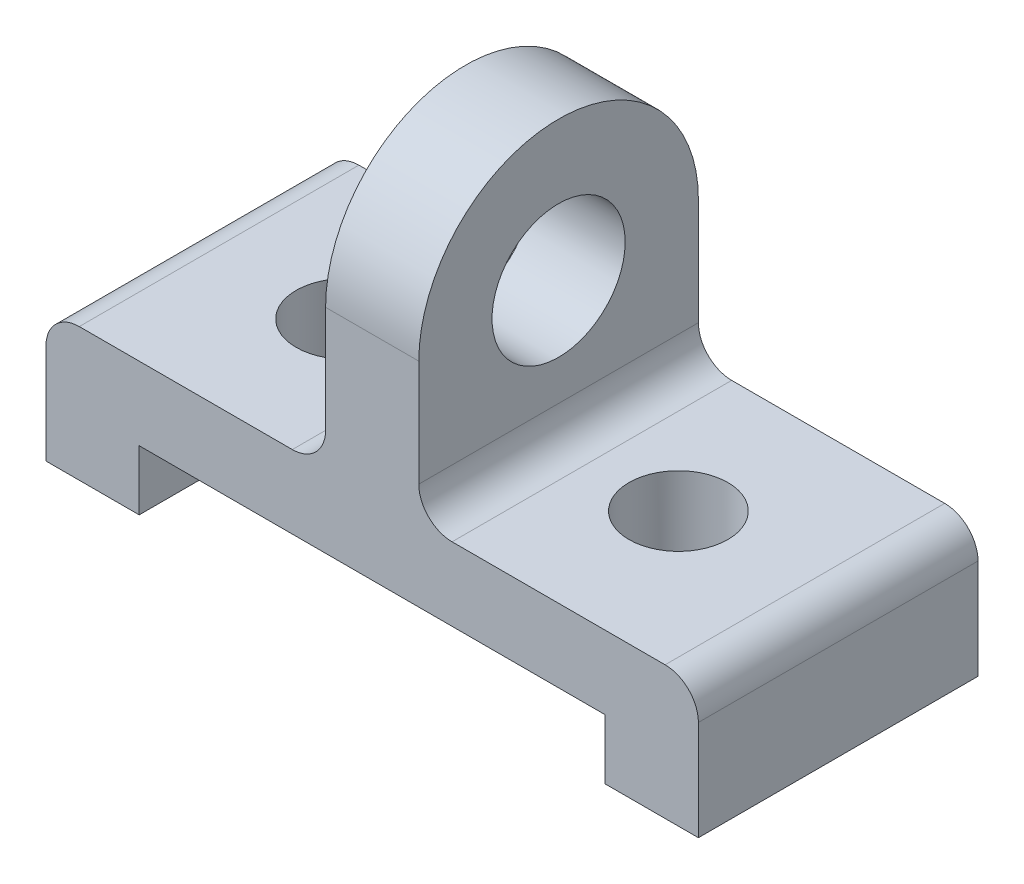
SolidWorks part; units mm, degrees
ref_plane "Front Plane" through (0, 0, 0) normal (0, 0, 1) x (1, 0, 0)
ref_plane "Top Plane" through (0, 0, 0) normal (0, 1, 0) x (1, 0, 0)
ref_plane "Right Plane" through (0, 0, 0) normal (1, 0, 0) x (0, 0, -1)
sketch "Sketch1" plane through (0, 0, 0) normal (0, 1, 0) x (1, 0, 0)
  line L1 (-49, -21) -> (49, -21)
  line L2 (-49, -21) -> (-49, 21)
  line L3 (-49, 21) -> (49, 21)
  line L4 (49, -21) -> (49, 21)
  line L5 (-49, -21) -> (49, 21) construction
  line L6 (-49, 21) -> (49, -21) construction
  point P0 (0, 0)
  dimension "D1" = 98
  dimension "D2" = 42
extrude "Boss-Extrude1" add sketch "Sketch1" along normal blind 20
sketch "Sketch2" plane through (0, 0, 21) normal (0, 0, 1) x (1, 0, 0)
  line L0 (-49, 0) -> (49, 0) construction
  line L1 (-35, 0) -> (35, 0)
  line L2 (-35, 0) -> (-35, 9)
  line L3 (-35, 9) -> (35, 9)
  line L4 (35, 0) -> (35, 9)
  dimension "D1" = 14
  dimension "D2" = 14
  dimension "D3" = 9
extrude "Cut-Extrude1" cut sketch "Sketch2" against normal through all
sketch "Sketch3" plane through (0, 0, 0) normal (1, 0, 0) x (0, 0, -1)
  line L1 (-21, 20) -> (21, 20)
  line L2 (-21, 20) -> (-21, 62)
  line L3 (-21, 62) -> (21, 62)
  line L4 (21, 20) -> (21, 62)
  dimension "D1" = 42
extrude "Boss-Extrude2" add sketch "Sketch3" along normal mid plane 14
fillet "Fillet1" 2 edges at (0, 62, 21) (0, 62, -21) type full round first side face at (0, 18.5, 21) second side face at (0, 18.5, -21) middle face at (0, 62, 0)
sketch "Sketch4" plane through (7, 0, 0) normal (1, 0, 0) x (0, 0, -1)
  line L1 (-21, 41) -> (21, 41) construction
  circle A0 centre (0, 41) radius 10
extrude "Cut-Extrude2" cut sketch "Sketch4" against normal through all
sketch "Sketch5" plane through (0, 20, 0) normal (0, 1, 0) x (1, 0, 0)
  line L1 (0, 36.1063) -> (0, -35.8936) construction
  circle A0 centre (-25, 0) radius 7.4243
  circle A1 centre (25, 0) radius 7.4243
  dimension "D1" = 50
extrude "Cut-Extrude5" cut sketch "Sketch5" against normal through all
fillet "Fillet2" radius 5 4 edges at (-49, 20, 0) (49, 20, 0) (7, 20, 0) (-7, 20, 0)
